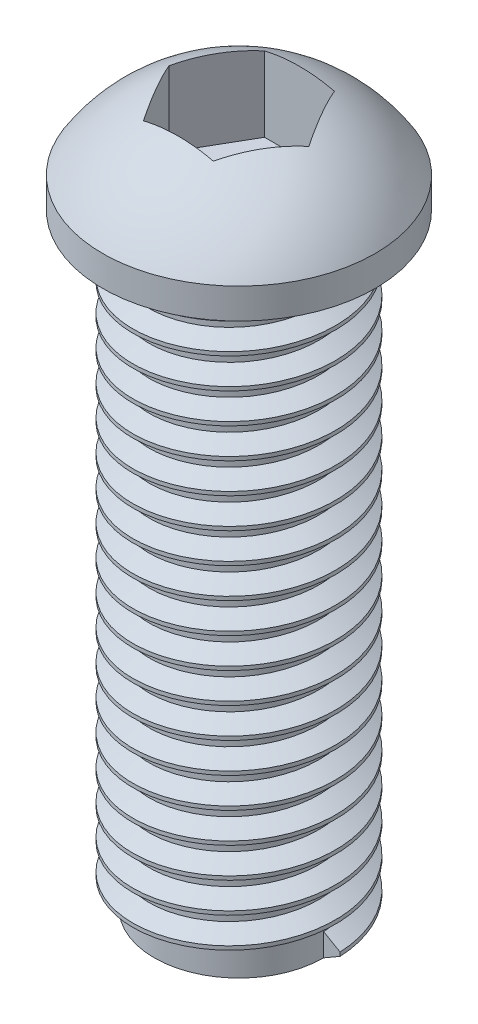
SolidWorks part; units mm, degrees
ref_plane "Front Plane" through (0, 0, 0) normal (0, 0, 1) x (1, 0, 0)
ref_plane "Top Plane" through (0, 0, 0) normal (0, 1, 0) x (1, 0, 0)
ref_plane "Right Plane" through (0, 0, 0) normal (1, 0, 0) x (0, 0, -1)
sketch "Sketch1" plane through (0, 0, 0) normal (0, 1, 0) x (1, 0, 0)
  circle A0 centre (0, 0) radius 1.4
  dimension "D1" = 2.8
extrude "Boss-Extrude1" add sketch "Sketch1" against normal blind 10
sketch "Sketch2" plane through (0, 0, 0) normal (0, 0, 1) x (1, 0, 0)
  line L0 (0, 0) -> (2.25, 0)
  line L1 (2.25, 0) -> (2.25, 0.5)
  line L2 (0, 0) -> (0, 1.75)
  arc A0 (0, 1.75) -> (2.25, 0.5) centre (0, -0.9) cw
  dimension "D1" = 2.25
  dimension "D2" = 0.5
  dimension "D3" = 1.75
revolve "Revolve1" add sketch "Sketch2" angle 360 about L2
sketch "Sketch3" plane through (0, 0, 0) normal (0, 1, 0) x (1, 0, 0)
  line L1 (1.1547, 0) -> (0.5774, 1)
  line L2 (0.5774, 1) -> (-0.5774, 1)
  line L3 (-0.5774, 1) -> (-1.1547, 0)
  line L4 (-1.1547, 0) -> (-0.5774, -1)
  line L5 (-0.5774, -1) -> (0.5774, -1)
  line L6 (0.5774, -1) -> (1.1547, 0)
  circle A0 centre (0, 0) radius 1 construction
  dimension "D1" = 2
  dimension "D2" = 1
extrude "Cut-Extrude1" cut sketch "Sketch3" against normal blind 1.5 from offset 1.75
thread "Thread2" pitch 0.5 method extrude profile "Thread Profile2" start angle 0, offset 0, length 0, pitch 0.5, diameter 2.8
ref_plane "Plane2" through (1.4, -10, 0) normal (0, 0, 1) x (1, 0, 0)
sketch "Thread Profile2" plane through (1.4, -10, 0) normal (0, 0, 1) x (1, 0, 0)
  line L0 (0, 0) -> (0, 0.5) construction
  line L1 (0, 0) -> (0.2706, 0.1562)
  line L2 (0.2706, 0.1562) -> (0.2706, 0.2187)
  line L3 (0.2706, 0.2187) -> (0, 0.375)
  line L4 (0.2706, 0.1875) -> (0, 0.1875) construction
  line L11 (0, 0) -> (0, 0.375)
  point P2 (0, 0)
  dimension "Pitch" = 0.5
  dimension "Profile_Angle" = 60
  dimension "Profile_Land" = 0.0625
  dimension "Profile_Height" = 0.2706
